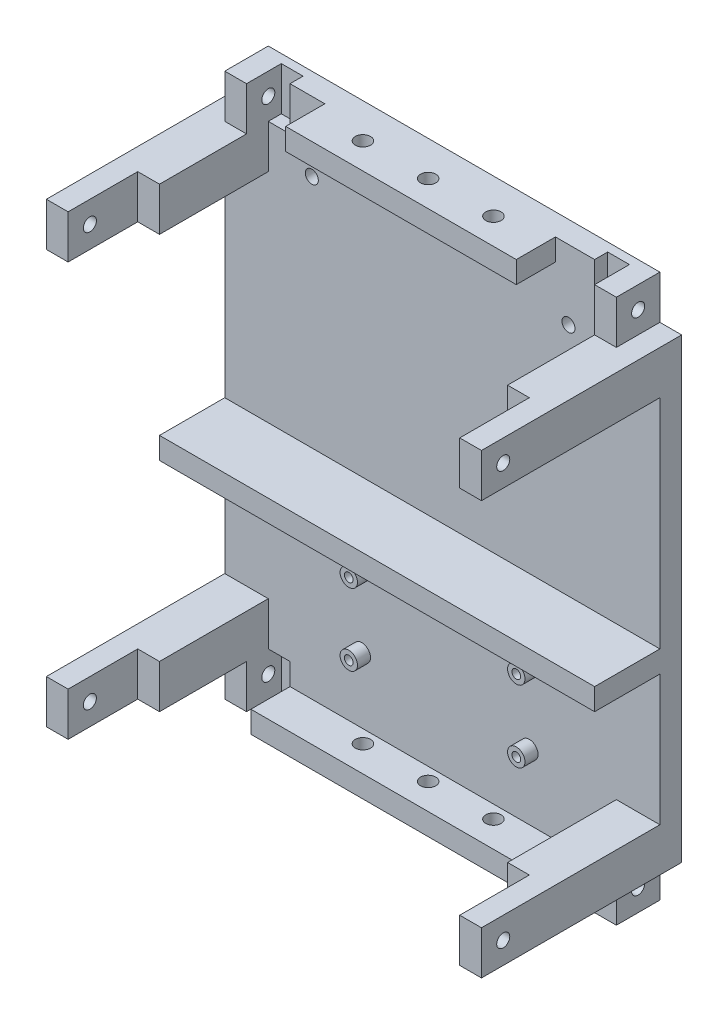
SolidWorks part; units mm, degrees
ref_plane "Front Plane" through (0, 0, 0) normal (0, 0, 1) x (1, 0, 0)
ref_plane "Top Plane" through (0, 0, 0) normal (0, 1, 0) x (1, 0, 0)
ref_plane "Right Plane" through (0, 0, 0) normal (1, 0, 0) x (0, 0, -1)
sketch "Sketch1" plane through (0, 0, 0) normal (0, 0, 1) x (1, 0, 0)
  line L1 (-95, 125) -> (-5, 125)
  line L2 (-95, 125) -> (-95, 0)
  line L3 (-95, 0) -> (-5, 0)
  line L4 (-5, 125) -> (-5, 0)
extrude "Boss-Extrude1" add sketch "Sketch1" along normal blind 5
sketch "Sketch2" plane through (-95, 0, 0) normal (-1, 0, 0) x (0, 0, 1)
  line L0 (10, 115) -> (0, 115) construction
  line L1 (5, 115) -> (0, 115)
  line L2 (5, 115) -> (5, 10)
  line L3 (5, 10) -> (0, 10)
  line L4 (0, 115) -> (0, 10)
  line L5 (0, 125) -> (0, 0) construction
  line L6 (10, 10) -> (0, 10) construction
extrude "Boss-Extrude2" add sketch "Sketch2" along normal up to surface (5 mm away)
sketch "Sketch3" plane through (0, 0, 5) normal (0, 0, 1) x (1, 0, 0)
  line L1 (-5, 125) -> (-10, 125)
  line L2 (-5, 125) -> (-5, 115)
  line L3 (-5, 115) -> (-10, 115)
  line L4 (-10, 125) -> (-10, 115)
  line L5 (-95, 125) -> (-90, 125)
  line L6 (-95, 125) -> (-95, 115)
  line L7 (-95, 115) -> (-90, 115)
  line L8 (-90, 125) -> (-90, 115)
  line L9 (-5, 0) -> (-10, 0)
  line L10 (-5, 0) -> (-5, 10)
  line L11 (-5, 10) -> (-10, 10)
  line L12 (-10, 0) -> (-10, 10)
  line L13 (-95, 0) -> (-90, 0)
  line L14 (-95, 0) -> (-95, 10)
  line L15 (-95, 10) -> (-90, 10)
  line L16 (-90, 0) -> (-90, 10)
  dimension "D1" = 5
  dimension "D2" = 10
extrude "Boss-Extrude3" add sketch "Sketch3" along normal up to surface (5 mm away)
sketch "Sketch4" plane through (0, 0, 5) normal (0, 0, 1) x (1, 0, 0)
  line L0 (-90, 0) -> (-10, 0) construction
  line L1 (-90, 125) -> (-85, 125)
  line L2 (-90, 125) -> (-90, 115)
  line L3 (-90, 115) -> (-85, 115)
  line L4 (-85, 125) -> (-85, 115)
  line L5 (-10, 125) -> (-15, 125)
  line L6 (-10, 125) -> (-10, 115)
  line L7 (-10, 115) -> (-15, 115)
  line L8 (-15, 125) -> (-15, 115)
  line L9 (-10, 0) -> (-15, 0)
  line L10 (-10, 0) -> (-10, 10)
  line L11 (-10, 10) -> (-15, 10)
  line L12 (-15, 0) -> (-15, 10)
  line L13 (-90, 0) -> (-85, 0)
  line L14 (-90, 0) -> (-90, 10)
  line L15 (-90, 10) -> (-85, 10)
  line L16 (-85, 0) -> (-85, 10)
  dimension "D1" = 5
  dimension "D2" = 10
extrude "Cut-Extrude1" cut sketch "Sketch4" against normal blind 3
sketch "Sketch5" plane through (0, 0, 0) normal (1, 0, 0) x (0, 0, -1)
  circle A0 centre (-5, 5) radius 1.5
  circle A1 centre (-5, 120) radius 1.5
extrude "Cut-Extrude2" cut sketch "Sketch5" against normal up to surface (15 mm away) up to face at (-15, 5, 3.5)
sketch "Sketch6" plane through (-100, 0, 0) normal (-1, 0, 0) x (0, 0, 1)
  circle A0 centre (5, 5) radius 1.5
  circle A1 centre (5, 120) radius 1.5
extrude "Cut-Extrude3" cut sketch "Sketch6" against normal up to surface (15 mm away) up to face at (-85, 120, 3.5)
sketch "Sketch7" plane through (0, 0, 5) normal (0, 0, 1) x (1, 0, 0)
  line L0 (-15, 125) -> (-85, 125) construction
  line L1 (-77, 125) -> (-24, 125)
  line L2 (-77, 125) -> (-77, 120)
  line L3 (-77, 120) -> (-24, 120)
  line L4 (-24, 125) -> (-24, 120)
  line L5 (-85, 0) -> (-85, 10) construction
  line L6 (-85, 0) -> (-15, 0)
  line L7 (-85, 0) -> (-85, 5)
  line L8 (-85, 5) -> (-15, 5)
  line L9 (-15, 0) -> (-15, 5)
  line L10 (-15, 10) -> (-15, 0) construction
  line L11 (-85, 0) -> (-15, 0) construction
  dimension "D1" = 0
  dimension "D2" = 5
  dimension "D3" = 5
extrude "Boss-Extrude4" add sketch "Sketch7" along normal up to surface (9 mm away)
sketch "Sketch8" plane through (0, 0, 0) normal (0, -1, 0) x (1, 0, 0)
  circle A0 centre (-65.25, 8) radius 1.75
  circle A1 centre (-50.25, 8) radius 1.75
  circle A2 centre (-35.25, 8) radius 1.75
extrude "Cut-Extrude4" cut sketch "Sketch8" against normal up to surface (125 mm away) up to face at (-49.5937, 125, 6.25)
sketch "Sketch11" plane through (-5, 0, 0) normal (1, 0, 0) x (0, 0, -1)
  line L0 (0, 0) -> (0, 125) construction
  line L1 (-5, 115) -> (0, 115)
  line L2 (-5, 115) -> (-5, 10)
  line L3 (-5, 10) -> (0, 10)
  line L4 (0, 115) -> (0, 10)
extrude "Boss-Extrude5" add sketch "Sketch11" along normal blind 5
sketch "Sketch12" plane through (0, 0, 0) normal (0, 0, -1) x (-1, 0, 0)
  line L0 (5, 125) -> (95, 125) construction
  line L1 (77, 103) -> (83.5, 103)
  line L2 (77, 103) -> (77, 120)
  line L3 (77, 120) -> (83.5, 120)
  line L4 (83.5, 103) -> (83.5, 120)
  line L5 (24, 103) -> (17.5, 103)
  line L6 (24, 103) -> (24, 120)
  line L7 (24, 120) -> (17.5, 120)
  line L8 (17.5, 103) -> (17.5, 120)
  line L11 (85, 115) -> (85, 125) construction
  dimension "D1" = 17
  dimension "D2" = 6.5
  dimension "D3" = 17
  dimension "D4" = 6.5
  dimension "D5" = 5
  dimension "D6" = 53
  dimension "D7" = 8
extrude "Cut-Extrude7" cut sketch "Sketch12" against normal blind 2
sketch "Sketch13" plane through (0, 0, 2) normal (0, 0, -1) x (-1, 0, 0)
  line L0 (17.5, 103) -> (24, 103) construction
  line L1 (24, 103) -> (24, 120) construction
  line L2 (77, 120) -> (77, 103) construction
  circle A0 centre (80, 109) radius 1.5
  circle A1 centre (21, 109) radius 1.5
  dimension "D2" = 3
  dimension "D3" = 3
  dimension "D4" = 3
  dimension "D1" = 6
extrude "Cut-Extrude8" cut sketch "Sketch13" against normal up to surface (3 mm away) up to face at (-49.9375, 72.9167, 5)
sketch "Sketch14" plane through (0, 0, 5) normal (0, 0, 1) x (1, 0, 0)
  line L0 (0, 115) -> (0, 10) construction
  line L1 (-15, 5) -> (-85, 5) construction
  circle A0 centre (-68.5, 20) radius 1
  circle A1 centre (-30, 20) radius 1
  circle A2 centre (-68.5, 36.5) radius 1
  circle A3 centre (-30, 36.5) radius 1
  dimension "D1" = 2
  dimension "D2" = 16.5
  dimension "D3" = 38.5
  dimension "D4" = 30
  dimension "D5" = 15
extrude "Cut-Extrude9" cut sketch "Sketch14" against normal up to surface (5 mm away) up to face at (-20.75, 111.5, 0)
sketch "Sketch15" plane through (0, 0, 5) normal (0, 0, 1) x (1, 0, 0)
  circle A0 centre (-30, 36.5) radius 1
  circle A1 centre (-68.5, 36.5) radius 1
  circle A2 centre (-68.5, 36.5) radius 2
  circle A3 centre (-30, 36.5) radius 2
  circle A4 centre (-30, 20) radius 1
  circle A5 centre (-68.5, 20) radius 1
  circle A6 centre (-68.5, 20) radius 2
  circle A7 centre (-30, 20) radius 2
  dimension "D1" = 4
extrude "Boss-Extrude6" add sketch "Sketch15" along normal blind 3
sketch "Sketch16" plane through (0, 0, 5) normal (0, 0, 1) x (1, 0, 0)
  line L1 (0, 10) -> (-10, 10)
  line L2 (0, 10) -> (0, 20)
  line L3 (0, 20) -> (-10, 20)
  line L4 (-10, 10) -> (-10, 20)
  line L5 (-100, 10) -> (-90, 10)
  line L6 (-100, 10) -> (-100, 20)
  line L7 (-100, 20) -> (-90, 20)
  line L8 (-90, 10) -> (-90, 20)
  line L9 (-100, 115) -> (-90, 115)
  line L10 (-100, 115) -> (-100, 105)
  line L11 (-100, 105) -> (-90, 105)
  line L12 (-90, 115) -> (-90, 105)
  line L13 (0, 115) -> (-10, 115)
  line L14 (0, 115) -> (0, 105)
  line L15 (0, 105) -> (-10, 105)
  line L16 (-10, 115) -> (-10, 105)
  dimension "D1" = 10
  dimension "D2" = 10
extrude "Boss-Extrude7" add sketch "Sketch16" along normal blind 25
sketch "Sketch17" plane through (0, 0, 30) normal (0, 0, 1) x (1, 0, 0)
  line L0 (0, 115) -> (-10, 115) construction
  line L1 (0, 105) -> (-5, 105)
  line L2 (0, 105) -> (0, 115)
  line L3 (0, 115) -> (-5, 115)
  line L4 (-5, 105) -> (-5, 115)
  line L5 (-90, 115) -> (-100, 115) construction
  line L6 (-100, 105) -> (-95, 105)
  line L7 (-100, 105) -> (-100, 115)
  line L8 (-100, 115) -> (-95, 115)
  line L9 (-95, 105) -> (-95, 115)
  line L10 (-90, 20) -> (-100, 20) construction
  line L11 (-100, 10) -> (-95, 10)
  line L12 (-100, 10) -> (-100, 20)
  line L13 (-100, 20) -> (-95, 20)
  line L14 (-95, 10) -> (-95, 20)
  line L17 (-10, 10) -> (0, 10) construction
  line L19 (-5, 10) -> (0, 10)
  line L20 (-5, 10) -> (-5, 20)
  line L22 (-5, 20) -> (0, 20)
  line L23 (0, 10) -> (0, 20)
extrude "Boss-Extrude8" add sketch "Sketch17" along normal blind 16
sketch "Sketch18" plane through (-100, 0, 0) normal (-1, 0, 0) x (0, 0, 1)
  line L0 (46, 105) -> (5, 105) construction
  line L1 (46, 115) -> (46, 105) construction
  line L2 (46, 10) -> (0, 10) construction
  circle A0 centre (41, 110) radius 1.5
  circle A1 centre (41, 15) radius 1.5
  dimension "D1" = 3
  dimension "D3" = 5
  dimension "D2" = 5
  dimension "D4" = 5
extrude "Cut-Extrude10" cut sketch "Sketch18" against normal through all
sketch "Sketch19" plane through (0, 0, 5) normal (0, 0, 1) x (1, 0, 0)
  line L0 (-100, 105) -> (-100, 20) construction
  line L1 (-100, 55) -> (0, 55)
  line L2 (-100, 55) -> (-100, 50)
  line L3 (-100, 50) -> (0, 50)
  line L4 (0, 55) -> (0, 50)
  line L5 (0, 105) -> (0, 20) construction
  line L6 (-10, 105) -> (0, 105) construction
  dimension "D1" = 5
  dimension "D2" = 50
extrude "Boss-Extrude9" add sketch "Sketch19" along normal blind 15
